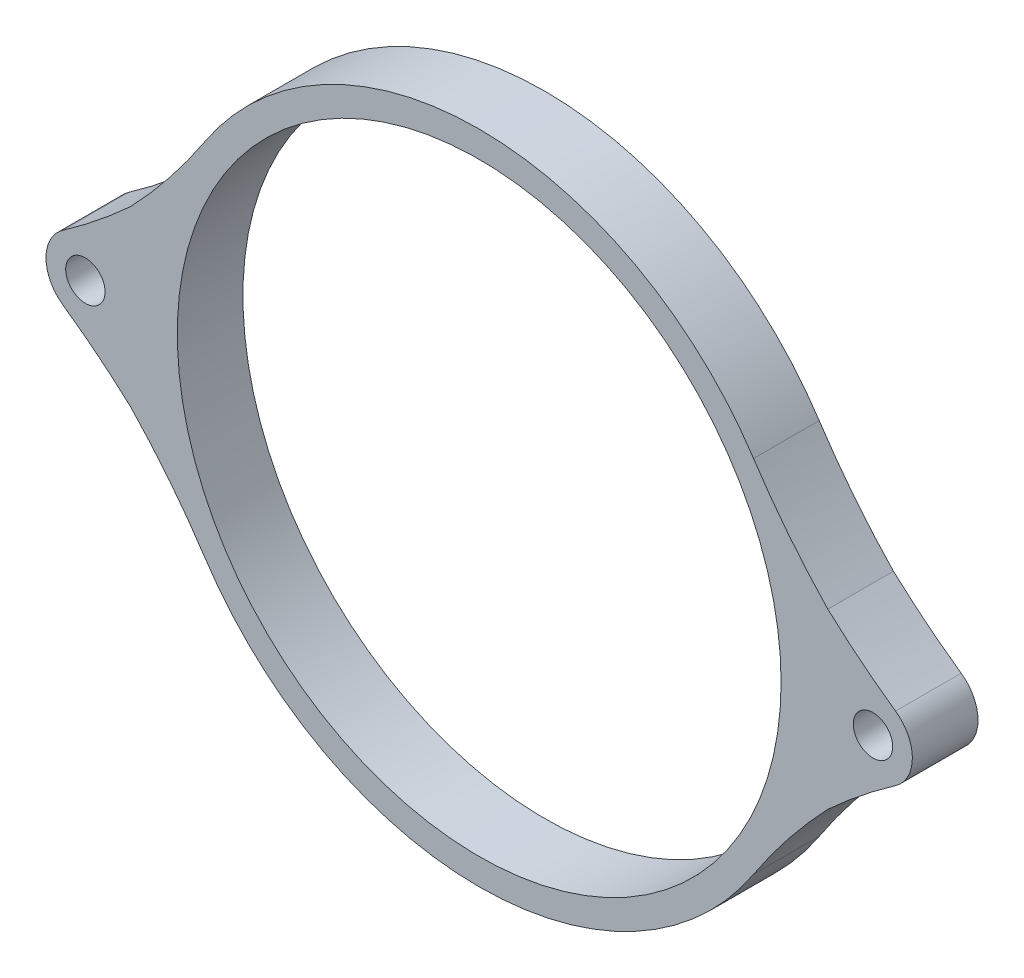
SolidWorks part; units mm, degrees
ref_plane "Plan de face" through (0, 0, 0) normal (0, 0, 1) x (1, 0, 0)
ref_plane "Plan de dessus" through (0, 0, 0) normal (0, 1, 0) x (1, 0, 0)
ref_plane "Plan de droite" through (0, 0, 0) normal (1, 0, 0) x (0, 0, -1)
sketch "Esquisse1" plane through (0, 0, 0) normal (0, 0, 1) x (1, 0, 0)
  line L0 (-30, 3) -> (-22.5479, 10.7977)
  line L7 (-30, -3) -> (-22.5479, -10.7977)
  line L8 (30, 3) -> (22.5479, 10.7977)
  line L9 (30, -3) -> (22.5479, -10.7977)
  circle A0 centre (0, 0) radius 25
  circle A1 centre (0, 0) radius 23
  circle A2 centre (30, 0) radius 1.5
  circle A3 centre (-30, 0) radius 1.5
  circle A4 centre (-30, 0) radius 3
  circle A5 centre (30, 0) radius 3
  dimension "D1" = 50
  dimension "D2" = 46
  dimension "D3" = 3
  dimension "D4" = 3
  dimension "D5" = 6
  dimension "D6" = 6
  dimension "D7" = 30
  dimension "D8" = 30
extrude "Boss.-Extru.1" add sketch "Esquisse1" along normal blind 5 contours A0 A1 | A4 L7 A0 L0 | A5 L8 A0 L9 | A5 A2 | A4 A3 region at (-26.1024, 0, 0) region at (-27.9387, 2.0613, 0) region at (0, 24.2929, 0) region at (26.1024, 0, 0) region at (32.0613, 2.0613, 0)
fillet "Congé1" radius 50 4 edges at (22.5479, -10.7977, 2.5) (22.5479, 10.7977, 2.5) (-22.5479, 10.7977, 2.5) (-22.5479, -10.7977, 2.5)
fillet "Congé2" radius 50 4 edges at (30, -3, 2.5) (30, 3, 2.5) (-30, 3, 2.5) (-30, -3, 2.5)
